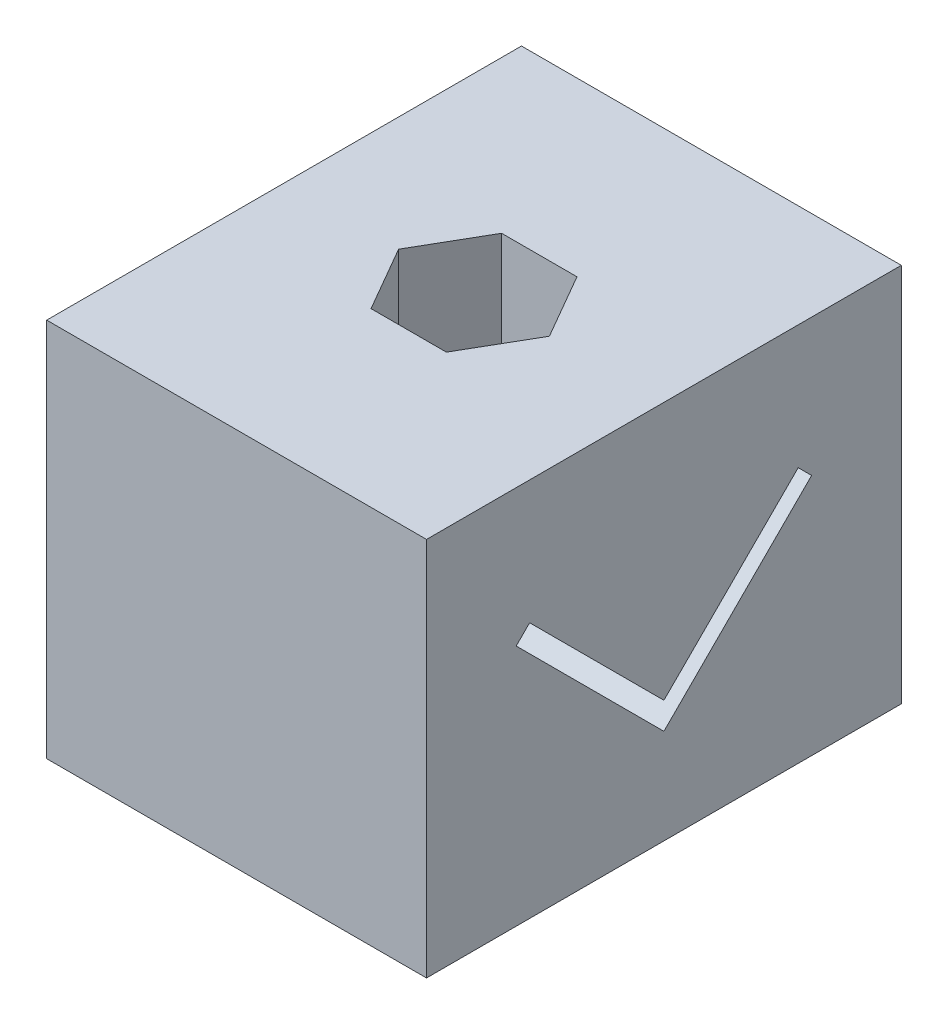
SolidWorks part; units mm, degrees
material "ABS"
ref_plane "Front Plane" through (0, 0, 0) normal (0, 0, 1) x (1, 0, 0)
ref_plane "Top Plane" through (0, 0, 0) normal (0, 1, 0) x (1, 0, 0)
ref_plane "Right Plane" through (0, 0, 0) normal (1, 0, 0) x (0, 0, -1)
sketch "Sketch1" plane through (0, 0, 0) normal (0, 0, 1) x (1, 0, 0)
  line L0 (0, 0) -> (12.7, 0)
  line L1 (12.7, 0) -> (12.7, 25.4)
  line L2 (12.7, 25.4) -> (-12.7, 25.4)
  line L3 (-12.7, 25.4) -> (-12.7, 0)
  line L4 (-12.7, 0) -> (0, 0)
  dimension "D1" = 25.4
  dimension "D2" = 25.4
extrude "Boss-Extrude1" add sketch "Sketch1" along normal mid plane 31.75
sketch "Sketch2" plane through (-12.7, 0, 0) normal (-1, 0, 0) x (0, 0, 1)
  line L0 (0, 8.1461) -> (-8.9803, 17.1263)
  line L1 (-8.9803, 17.1263) -> (-9.8783, 16.2283)
  line L2 (-9.8783, 16.2283) -> (0, 6.35)
  line L3 (0, 6.35) -> (9.8783, 16.2283)
  line L4 (9.8783, 16.2283) -> (8.9803, 17.1263)
  line L5 (8.9803, 17.1263) -> (0, 8.1461)
  line L6 (-11.3146, 0) -> (21.0706, 0) construction
  line L7 (-15.875, 25.4) -> (-15.875, 0) construction
  line L8 (-9.8783, 16.2283) -> (-15.875, 16.2283) construction
  line L9 (9.8783, 16.2283) -> (15.875, 16.2283) construction
  line L10 (15.875, 25.4) -> (15.875, 0) construction
  dimension "D1" = 1.27
  dimension "D2" = 6.35
  dimension "D3" = 12.7
extrude "Cut-Extrude1" cut sketch "Sketch2" against normal blind 152.4
hole_wizard "1/4 (0.25) Diameter Hole1" positions "Sketch5" profile "Sketch6" hole size "1/4" standard "ANSI Inch" end condition through all
sketch "Sketch5" plane through (0, 25.4, 0) normal (0, 1, 0) x (1, 0, 0)
  line L0 (-12.7, -15.875) -> (-12.7, 15.875) construction
  point P0 (0, 0)
  point P2 (76.2, 0)
  dimension "D1" = 12.7
  dimension "D2" = 76.2
sketch "Sketch6" plane through (0, 25.4, 0) normal (1, 0, 0) x (0, 0, 1)
  line L0 (0, 0) -> (0, 25.4)
  line L1 (0, 25.4) -> (1.9844, 25.4)
  line L2 (1.9844, 25.4) -> (1.9844, 0)
  line L5 (1.9844, 0) -> (0, 0)
  line L11 (0, -6.35) -> (0, 107.95) construction
  dimension "Thru Hole Dia." = 3.9688
  dimension "Thru Hole Depth" = 25.4
sketch "Sketch7" plane through (0, 25.4, 0) normal (0, 1, 0) x (1, 0, 0)
  line L1 (5.041, 0) -> (2.5205, 4.3656)
  line L2 (2.5205, 4.3656) -> (-2.5205, 4.3656)
  line L3 (-2.5205, 4.3656) -> (-5.041, 0)
  line L4 (-5.041, 0) -> (-2.5205, -4.3656)
  line L5 (-2.5205, -4.3656) -> (2.5205, -4.3656)
  line L6 (2.5205, -4.3656) -> (5.041, 0)
  circle A0 centre (0, 0) radius 4.3656 construction
  dimension "D1" = 8.7312
extrude "Cut-Extrude2" cut sketch "Sketch7" against normal blind 11.43
sketch "Sketch8" plane through (0, 0, 0) normal (0, -1, 0) x (1, 0, 0)
  circle A0 centre (0, 0) radius 3.9688
  dimension "D1" = 7.9375
extrude "Cut-Extrude3" cut sketch "Sketch8" against normal blind 5.08
